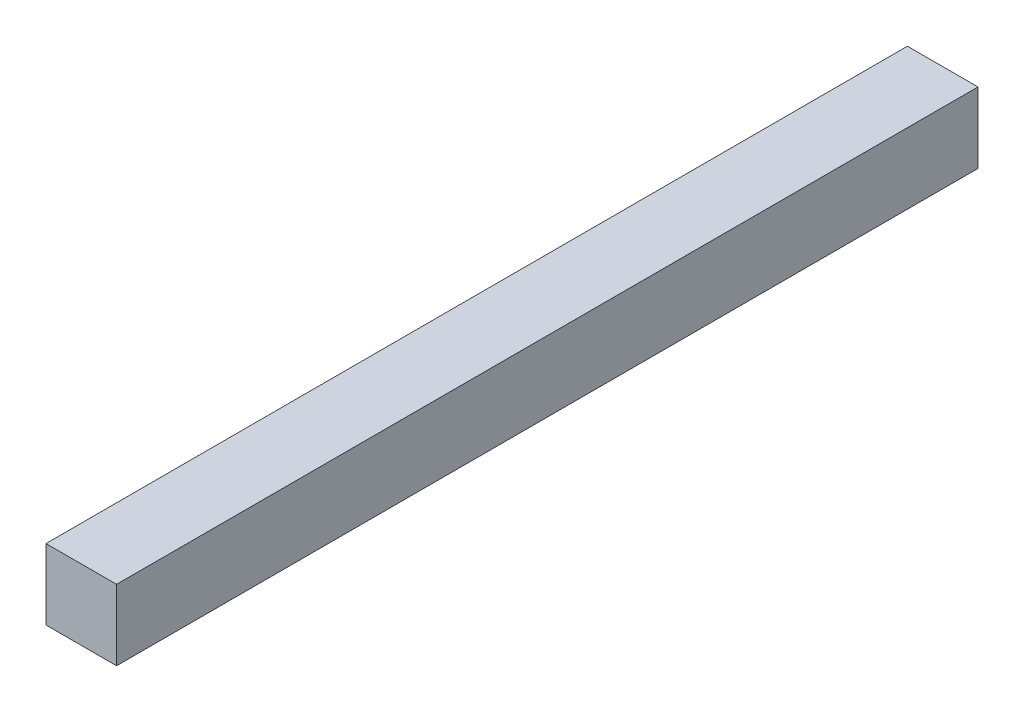
SolidWorks part; units mm, degrees
ref_plane "Front Plane" through (0, 0, 0) normal (0, 0, 1) x (1, 0, 0)
ref_plane "Top Plane" through (0, 0, 0) normal (0, 1, 0) x (1, 0, 0)
ref_plane "Right Plane" through (0, 0, 0) normal (1, 0, 0) x (0, 0, -1)
sketch "Sketch1" plane through (0, 0, 0) normal (0, 0, 1) x (1, 0, 0)
  line L1 (-6.35, -6.35) -> (6.35, -6.35)
  line L2 (-6.35, -6.35) -> (-6.35, 6.35)
  line L3 (-6.35, 6.35) -> (6.35, 6.35)
  line L4 (6.35, -6.35) -> (6.35, 6.35)
  line L5 (-6.35, -6.35) -> (6.35, 6.35) construction
  line L6 (-6.35, 6.35) -> (6.35, -6.35) construction
  point P0 (0, 0)
  dimension "D1" = 12.7
extrude "Boss-Extrude1" add sketch "Sketch1" along normal blind 155
